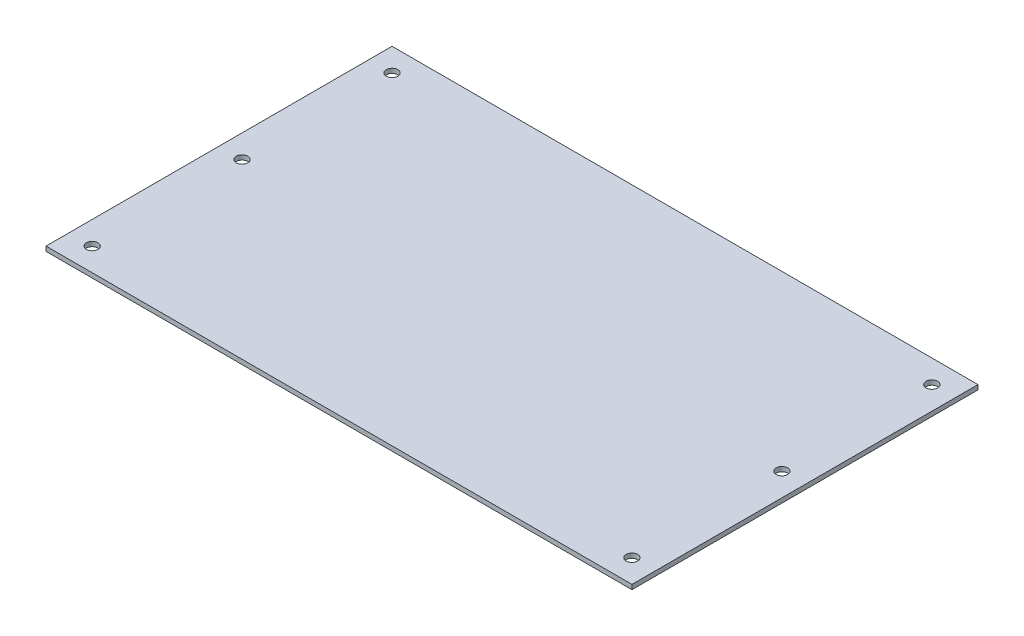
SolidWorks part; units mm, degrees
ref_plane "Płaszczyzna przednia" through (0, 0, 0) normal (0, 0, 1) x (1, 0, 0)
ref_plane "Płaszczyzna górna" through (0, 0, 0) normal (0, 1, 0) x (1, 0, 0)
ref_plane "Płaszczyzna prawa" through (0, 0, 0) normal (1, 0, 0) x (0, 0, -1)
sketch "Szkic1" plane through (0, 0, 0) normal (0, 1, 0) x (1, 0, 0)
  line L0 (-127, 75) -> (127, 75)
  line L1 (127, -75) -> (-127, -75)
  line L2 (-127, 75) -> (-127, -75)
  line L3 (127, 75) -> (127, -75)
  circle A0 centre (-117, 0) radius 2.5
  circle A1 centre (-117, 65) radius 2.5
  circle A2 centre (-117, -65) radius 2.5
  circle A3 centre (117, -65) radius 2.5
  circle A4 centre (117, 0) radius 2.5
  circle A5 centre (117, 65) radius 2.5
  point P0 (0, 0)
  line B0 (-127, 0) -> (-126, 0) construction
  line B1 (0, 65) -> (-1, 65) construction
  line B2 (0, -75) -> (0, -76) construction
  line B3 (-117, 0) -> (-117, -1) construction
  line B4 (117, -75) -> (117, -76) construction
  line B5 (102, -75) -> (102, -76) construction
  line B6 (-102, 0) -> (-102, -1) construction
  line B7 (-127, -75) -> (127, -75) construction
  line B8 (127, -75) -> (127, 75) construction
  line B9 (127, 75) -> (-127, 75) construction
  line B10 (-127, 75) -> (-127, -75) construction
  line B11 (-127, -65) -> (-126, -65) construction
  circle B12 centre (-117, 65) radius 2.5 construction
  circle B13 centre (-117, 0) radius 2.5 construction
  circle B14 centre (-117, -65) radius 2.5 construction
  circle B15 centre (117, -65) radius 2.5 construction
  circle B16 centre (117, 0) radius 2.5 construction
  circle B17 centre (117, 65) radius 2.5 construction
sketch_block_instance "boczek_pusty-1"
sketch_block "boczek_pusty"
extrude "Dodanie-wyciągnięcie1" add sketch "Szkic1" along normal blind 2 contours L3 L0 L2 L1 A5 A4 A3 A2 A1 A0 region at (0, 0, 0)
ref_axis "Oś1" through (117, 2, 65) along (0, -1, 0)
